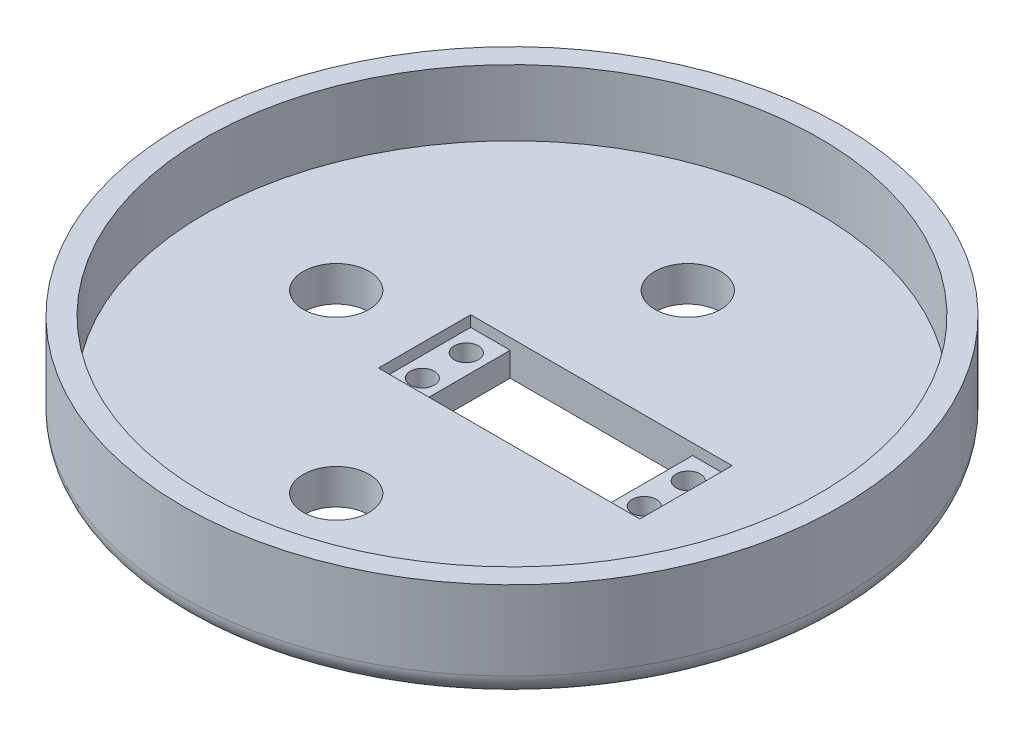
SolidWorks part; units mm, degrees
ref_plane "Front Plane" through (0, 0, 0) normal (0, 0, 1) x (1, 0, 0)
ref_plane "Top Plane" through (0, 0, 0) normal (0, 1, 0) x (1, 0, 0)
ref_plane "Right Plane" through (0, 0, 0) normal (1, 0, 0) x (0, 0, -1)
sketch "Sketch1" plane through (0, 0, 0) normal (0, 1, 0) x (1, 0, 0)
  circle A0 centre (0, 0) radius 75
  dimension "D1" = 150
extrude "Boss-Extrude1" add sketch "Sketch1" along normal blind 8
sketch "Sketch2" plane through (0, 8, 0) normal (0, 1, 0) x (1, 0, 0)
  line L1 (-10.9, 10.5) -> (30.6, 10.5)
  line L2 (-10.9, 10.5) -> (-10.9, -10.5)
  line L3 (-10.9, -10.5) -> (30.6, -10.5)
  line L4 (30.6, 10.5) -> (30.6, -10.5)
  dimension "D1" = 10.9
  dimension "D2" = 41.5
  dimension "D3" = 21
  dimension "D4" = 10.5
sketch "Sketch5" plane through (0, 8, 0) normal (0, 1, 0) x (1, 0, 0)
  circle A0 centre (0, 0) radius 70
  circle A1 centre (0, 0) radius 75
  dimension "D1" = 140
extrude "Boss-Extrude2" add sketch "Sketch5" along normal blind 15
extrude "Cut-Extrude6" cut sketch "Sketch2" against normal through all both and the other way through all
sketch "Sketch8" plane through (0, 8, 0) normal (0, 1, 0) x (1, 0, 0)
  line L0 (9.85, 16.633) -> (9.85, -16.695) construction
  line L1 (-10.9, 10.5) -> (-19.9, 10.5)
  line L2 (-10.9, 10.5) -> (-10.9, -10.5)
  line L3 (-10.9, -10.5) -> (-19.9, -10.5)
  line L4 (-19.9, 10.5) -> (-19.9, -10.5)
  line L5 (39.6, 10.5) -> (39.6, -10.5)
  line L6 (30.6, -10.5) -> (39.6, -10.5)
  line L7 (30.6, 10.5) -> (30.6, -10.5)
  line L8 (30.6, 10.5) -> (39.6, 10.5)
  circle A0 centre (-15.4, 5) radius 2.75
  circle A1 centre (-15.4, -5) radius 2.75
  circle A2 centre (35.1, -5) radius 2.75
  circle A3 centre (35.1, 5) radius 2.75
  dimension "D2" = 5.5
  dimension "D3" = 5.5
  dimension "D1" = 9
  dimension "D4" = 10
  dimension "D5" = 5.5
  dimension "D6" = 20.75
  dimension "D7" = 50.5
  dimension "D8" = 50.5
extrude "Cut-Extrude7" cut sketch "Sketch8" against normal blind 2.5
sketch "Sketch9" plane through (0, 8, 0) normal (0, 1, 0) x (1, 0, 0)
  circle A0 centre (-15.4, 5) radius 2.75
  circle A1 centre (-15.4, -5) radius 2.75
  circle A2 centre (35.1, 5) radius 2.75
  circle A3 centre (35.1, -5) radius 2.75
extrude "Cut-Extrude8" cut sketch "Sketch9" against normal through all both and the other way through all
fillet "Fillet2" radius 5 1 edges at (0, 0, 75)
sketch "Sketch11" plane through (0, 0, 0) normal (0, -1, 0) x (1, 0, 0)
  circle A0 centre (0, 40) radius 7.5
  circle A1 centre (0, -40) radius 7.5
  circle A2 centre (-40, 0) radius 7.5
  dimension "D4" = 15
  dimension "D5" = 15
  dimension "D6" = 15
  dimension "D1" = 40
  dimension "D2" = 40
  dimension "D3" = 40
  dimension "D7" = 90
  dimension "D8" = 90
extrude "Cut-Extrude9" cut sketch "Sketch11" against normal blind 10
sketch "Sketch12" plane through (0, 0, 0) normal (0, -1, 0) x (1, 0, 0)
  circle A0 centre (0, 40) radius 7.5
